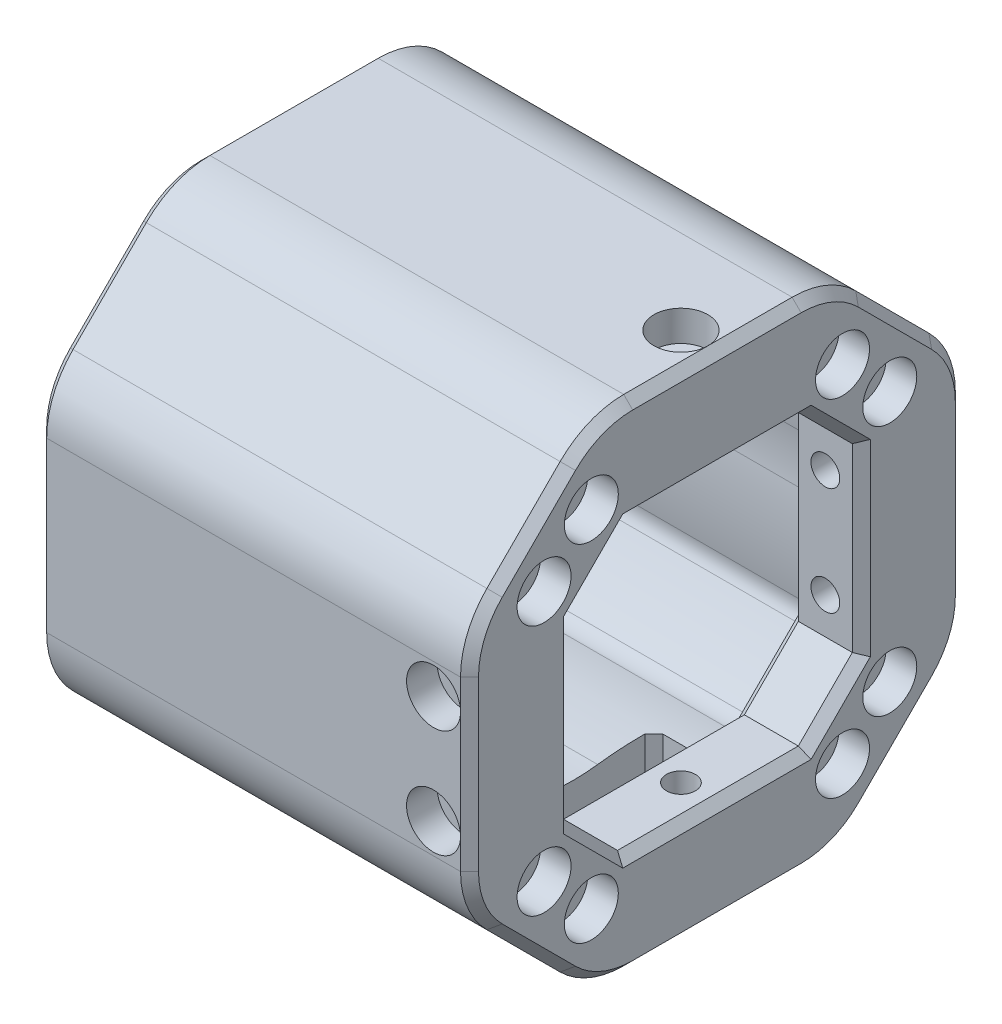
SolidWorks part; units mm, degrees
ref_plane "前视基准面" through (0, 0, 0) normal (0, 0, 1) x (1, 0, 0)
ref_plane "上视基准面" through (0, 0, 0) normal (0, 1, 0) x (1, 0, 0)
ref_plane "右视基准面" through (0, 0, 0) normal (1, 0, 0) x (0, 0, -1)
other "Configuration Table"
sketch "草图1" plane through (0, 0, 0) normal (1, 0, 0) x (0, 0, -1)
  line L1 (-27.5, -27.5) -> (27.5, -27.5)
  line L2 (-27.5, -27.5) -> (-27.5, 27.5)
  line L3 (-27.5, 27.5) -> (27.5, 27.5)
  line L4 (27.5, -27.5) -> (27.5, 27.5)
  line L5 (0, 27.5) -> (0, -27.5) construction
  line L6 (-27.5, 0) -> (27.5, 0) construction
  line L7 (-16.05, 16.05) -> (16.05, 16.05)
  line L8 (-16.05, 16.05) -> (-16.05, -16.05)
  line L9 (-16.05, -16.05) -> (16.05, -16.05)
  line L10 (16.05, 16.05) -> (16.05, -16.05)
  line L11 (0, -16.05) -> (0, 16.05) construction
  line L12 (-16.05, 0) -> (16.05, 0) construction
  circle A0 centre (0, 0) radius 31.25 construction
  circle A8 centre (0, 0) radius 18.05 construction
  dimension "D1" = 62.5
  dimension "D2" = 55
  dimension "D3" = 55
  dimension "D5" = 36.1
  dimension "D4" = 32.1
  dimension "D6" = 32.1
extrude "凸台-拉伸1" add sketch "草图1" along normal blind 8
sketch "草图2" plane through (8, 0, 0) normal (1, 0, 0) x (0, 0, -1)
  line L1 (0, 0) -> (13.9599, 19.2142) construction
  line L2 (0, 0) -> (23.75, 0) construction
  line L3 (0, 0) -> (0, 23.75) construction
  line L4 (0, 0) -> (19.2142, 13.9599) construction
  circle A1 centre (0, 0) radius 23.75 construction
  point P5 (13.9599, 19.2142)
  point P12 (19.2142, -13.9599)
  point P13 (-13.9599, -19.2142)
  point P14 (-19.2142, 13.9599)
  point P16 (19.2142, 13.9599)
  point P48 (13.9599, -19.2142)
  point P49 (-19.2142, -13.9599)
  point P50 (-13.9599, 19.2142)
  dimension "D1" = 47.5
  dimension "D2" = 4
  dimension "D3" = 4
  dimension "D4" = 36
  dimension "D6" = 36
chamfer "倒角1" distance 14 angle 45 4 edges at (4, -27.5, 27.5) (4, -27.5, -27.5) (4, 27.5, -27.5) (4, 27.5, 27.5)
chamfer "倒角2" distance 6 angle 45 4 edges at (4, -16.05, 16.05) (4, -16.05, -16.05) (4, 16.05, -16.05) (4, 16.05, 16.05)
sketch "草图3" plane through (0, 27.5, 0) normal (0, 1, 0) x (1, 0, 0)
  line L3 (8, 13.5) -> (8, -13.5) construction
  line L5 (0, 13.5) -> (0, -13.5) construction
  line L6 (0, 0) -> (4, 0) construction
  point P0 (4, 0)
  dimension "D2" = 4
sketch "草图4" plane through (0, 0, -27.5) normal (0, 0, -1) x (-1, 0, 0)
  line L0 (-4, 13.5) -> (-4, -13.5) construction
  line L1 (0, 13.5) -> (-8, 13.5) construction
  line L2 (-8, -13.5) -> (0, -13.5) construction
  line L3 (-8, 0) -> (0, 0) construction
  line L4 (-8, -13.5) -> (-8, 13.5) construction
  point P0 (-4, 6)
  point P1 (-4, -6)
  dimension "D1" = 6
  dimension "D2" = 6
hole_wizard "M3 六角圆柱头螺钉的柱形沉头孔1" positions "草图2" profile "草图5" counterbore size "M3" standard "GB" end condition through all
sketch "草图5" plane through (8, 19.2142, 13.9599) normal (0, 1, 0) x (0, 0, -1)
  line L0 (0, 0) -> (0, 8)
  line L1 (0, 8) -> (1.6, 8)
  line L3 (1.6, 8) -> (1.6, 3.4)
  line L4 (1.6, 3.4) -> (3, 3.4)
  line L5 (3, 3.4) -> (3, 0)
  line L7 (3, 0) -> (0, 0)
  line L11 (0, -6.35) -> (0, 107.95) construction
  dimension "通孔孔直径" = 3.2
  dimension "通孔孔深度" = 8
  dimension "柱形沉头孔直径" = 6
  dimension "柱形沉头孔深度" = 3.4
hole_wizard "M3 六角圆柱头螺钉的柱形沉头孔2" positions "草图3" profile "草图8" counterbore size "M3" standard "GB" end condition up to next
sketch "草图8" plane through (4, 27.5, 0) normal (1, 0, 0) x (0, 0, 1)
  line L0 (0, 0) -> (0, 11.45)
  line L1 (0, 11.45) -> (1.6, 11.45)
  line L3 (1.6, 11.45) -> (1.6, 3.4)
  line L4 (1.6, 3.4) -> (3, 3.4)
  line L5 (3, 3.4) -> (3, 0)
  line L7 (3, 0) -> (0, 0)
  line L11 (0, -6.35) -> (0, 107.95) construction
  dimension "通孔孔直径" = 3.2
  dimension "通孔孔深度" = 11.45
  dimension "柱形沉头孔直径" = 6
  dimension "柱形沉头孔深度" = 3.4
hole_wizard "M3 六角圆柱头螺钉的柱形沉头孔3" positions "草图4" profile "草图9" counterbore size "M3" standard "GB" end condition up to next
sketch "草图9" plane through (4, 6, -27.5) normal (1, 0, 0) x (0, 1, 0)
  line L0 (0, 0) -> (0, 11.45)
  line L1 (0, 11.45) -> (1.6, 11.45)
  line L3 (1.6, 11.45) -> (1.6, 3.4)
  line L4 (1.6, 3.4) -> (3, 3.4)
  line L5 (3, 3.4) -> (3, 0)
  line L7 (3, 0) -> (0, 0)
  line L11 (0, -6.35) -> (0, 107.95) construction
  dimension "通孔孔直径" = 3.2
  dimension "通孔孔深度" = 11.45
  dimension "柱形沉头孔直径" = 6
  dimension "柱形沉头孔深度" = 3.4
sketch "草图10" plane through (0, 0, 27.5) normal (0, 0, 1) x (1, 0, 0)
  line L0 (4, 13.5) -> (4, -13.5) construction
  line L1 (8, 13.5) -> (0, 13.5) construction
  line L2 (0, -13.5) -> (8, -13.5) construction
  point P6 (4, 6)
  point P7 (4, -6)
  dimension "D1" = 6
  dimension "D2" = 6
hole_wizard "M3 六角圆柱头螺钉的柱形沉头孔4" positions "草图10" profile "草图11" counterbore size "M3" standard "GB" end condition up to next
sketch "草图11" plane through (4, -6, 27.5) normal (1, 0, 0) x (0, -1, 0)
  line L0 (0, 0) -> (0, 11.45)
  line L1 (0, 11.45) -> (1.6, 11.45)
  line L3 (1.6, 11.45) -> (1.6, 3.4)
  line L4 (1.6, 3.4) -> (3, 3.4)
  line L5 (3, 3.4) -> (3, 0)
  line L7 (3, 0) -> (0, 0)
  line L11 (0, -6.35) -> (0, 107.95) construction
  dimension "通孔孔直径" = 3.2
  dimension "通孔孔深度" = 11.45
  dimension "柱形沉头孔直径" = 6
  dimension "柱形沉头孔深度" = 3.4
sketch "草图12" plane through (0, -27.5, 0) normal (0, -1, 0) x (1, 0, 0)
  line L0 (4, 13.5) -> (4, -13.5) construction
  line L1 (8, 13.5) -> (0, 13.5) construction
  line L2 (0, -13.5) -> (8, -13.5) construction
  point P6 (4, 0)
hole_wizard "M3 六角圆柱头螺钉的柱形沉头孔5" positions "草图12" profile "草图13" counterbore size "M3" standard "GB" end condition up to next
sketch "草图13" plane through (4, -27.5, 0) normal (1, 0, 0) x (0, 0, -1)
  line L0 (0, 0) -> (0, 11.45)
  line L1 (0, 11.45) -> (1.6, 11.45)
  line L3 (1.6, 11.45) -> (1.6, 3.4)
  line L4 (1.6, 3.4) -> (3, 3.4)
  line L5 (3, 3.4) -> (3, 0)
  line L7 (3, 0) -> (0, 0)
  line L11 (0, -6.35) -> (0, 107.95) construction
  dimension "通孔孔直径" = 3.2
  dimension "通孔孔深度" = 11.45
  dimension "柱形沉头孔直径" = 6
  dimension "柱形沉头孔深度" = 3.4
fillet "圆角1" radius 10 8 edges at (4, 27.5, 13.5) (4, 13.5, 27.5) (4, 27.5, -13.5) (4, 13.5, -27.5) (4, -13.5, -27.5) (4, -27.5, -13.5) (4, -27.5, 13.5) (4, -13.5, 27.5)
chamfer "倒角4" distance 1 angle 45 24 edges at (8, 0, -16.05) (8, -13.05, -13.05) (8, 13.05, -13.05) (8, 16.05, 0) (8, 13.05, 13.05) (8, -16.05, 0) (8, -13.05, 13.05) (8, 0, 16.05) (8, 0, -27.5) (8, 13.1847, -26.7388) (8, -13.1847, -26.7388) (8, 20.5, -20.5) (8, -20.5, -20.5) (8, 26.7388, -13.1847) (8, -26.7388, -13.1847) (8, 27.5, 0) (8, -27.5, 0) (8, 26.7388, 13.1847) (8, -26.7388, 13.1847) (8, 20.5, 20.5) (8, -20.5, 20.5) (8, 13.1847, 26.7388) (8, -13.1847, 26.7388) (8, 0, 27.5)
ref_plane "基准面2" through (0, 0, 0) normal (-1, 0, 0) x (0, 0, 1)
sketch "草图16" plane through (0, 0, 0) normal (-1, 0, 0) x (0, 0, 1)
  line L8 (0, 0) -> (-21.85, 0) construction
  line L9 (0, 0) -> (0, 21.85) construction
  line L10 (0, 0) -> (0, -21.85) construction
  line L11 (0, 21.75) -> (0, 0) construction
  line L12 (0, 0) -> (21.85, 0) construction
  line L15 (13.9599, 19.2142) -> (0, 0) construction
  line L16 (0, 0) -> (20.5, 20.5) construction
  line L17 (0, -21.75) -> (0, -21.85)
  line L19 (0, 21.75) -> (0, 21.85)
  line L20 (24.5711, 16.4289) -> (16.4289, 24.5711) construction
  line L29 (24.5711, 16.4289) -> (16.4289, 24.5711)
  line L30 (9.3579, 27.5) -> (-9.3579, 27.5)
  line L31 (-16.4289, 24.5711) -> (-24.5711, 16.4289)
  line L32 (-27.5, 9.3579) -> (-27.5, -9.3579)
  line L33 (-24.5711, -16.4289) -> (-16.4289, -24.5711)
  line L34 (-9.3579, -27.5) -> (9.3579, -27.5)
  line L35 (16.4289, -24.5711) -> (24.5711, -16.4289)
  line L36 (27.5, -9.3579) -> (27.5, 9.3579)
  line L37 (24.5711, 16.4289) -> (16.4289, 24.5711)
  line L38 (9.3579, 27.5) -> (-9.3579, 27.5)
  line L39 (-16.4289, 24.5711) -> (-24.5711, 16.4289)
  line L40 (-27.5, 9.3579) -> (-27.5, -9.3579)
  line L41 (-24.5711, -16.4289) -> (-16.4289, -24.5711)
  line L42 (-9.3579, -27.5) -> (9.3579, -27.5)
  line L43 (16.4289, -24.5711) -> (24.5711, -16.4289)
  line L44 (27.5, -9.3579) -> (27.5, 9.3579)
  arc A0 (15.4294, 21.2367) -> (13.5954, 21.6874) centre (13.9599, 19.2142) ccw construction
  arc A1 (2.7345, 21.5774) -> (13.5954, 21.6874) centre (7.7635, 61.26) ccw construction
  arc A2 (2.7345, 21.5774) -> (-2.7345, 21.5774) centre (0, 0) ccw construction
  arc A3 (21.2367, 15.4294) -> (15.4294, 21.2367) centre (0, 0) ccw construction
  arc A4 (21.2367, 15.4294) -> (21.6874, 13.5954) centre (19.2142, 13.9599) cw construction
  arc A5 (21.5774, 2.7345) -> (21.6874, 13.5954) centre (61.26, 7.7635) cw construction
  arc A6 (21.5774, 2.7345) -> (21.5774, -2.7345) centre (0, 0) cw construction
  arc A7 (21.5774, -2.7345) -> (21.6874, -13.5954) centre (61.26, -7.7635) ccw construction
  arc A8 (21.2367, -15.4294) -> (21.6874, -13.5954) centre (19.2142, -13.9599) ccw construction
  arc A9 (21.2367, -15.4294) -> (15.4294, -21.2367) centre (0, 0) cw construction
  arc A10 (15.4294, -21.2367) -> (13.5954, -21.6874) centre (13.9599, -19.2142) cw construction
  arc A11 (2.7345, -21.5774) -> (13.5954, -21.6874) centre (7.7635, -61.26) cw construction
  arc A12 (2.7345, -21.5774) -> (-2.7345, -21.5774) centre (0, 0) cw construction
  arc A13 (-15.4294, -21.2367) -> (-13.5954, -21.6874) centre (-13.9599, -19.2142) ccw construction
  arc A14 (-2.7345, -21.5774) -> (-13.5954, -21.6874) centre (-7.7635, -61.26) ccw construction
  arc A15 (-21.2367, -15.4294) -> (-15.4294, -21.2367) centre (0, 0) ccw construction
  arc A16 (-21.2367, -15.4294) -> (-21.6874, -13.5954) centre (-19.2142, -13.9599) cw construction
  arc A17 (-21.5774, -2.7345) -> (-21.6874, -13.5954) centre (-61.26, -7.7635) cw construction
  arc A18 (-21.5774, 2.7345) -> (-21.5774, -2.7345) centre (0, 0) ccw construction
  arc A19 (-21.5774, 2.7345) -> (-21.6874, 13.5954) centre (-61.26, 7.7635) ccw construction
  arc A20 (-21.2367, 15.4294) -> (-21.6874, 13.5954) centre (-19.2142, 13.9599) ccw construction
  arc A21 (-21.2367, 15.4294) -> (-15.4294, 21.2367) centre (0, 0) cw construction
  arc A22 (-15.4294, 21.2367) -> (-13.5954, 21.6874) centre (-13.9599, 19.2142) cw construction
  arc A23 (-2.7345, 21.5774) -> (-13.5954, 21.6874) centre (-7.7635, 61.26) cw construction
  arc A25 (-2.7345, 21.5774) -> (0, 21.75) centre (0, 0) cw construction
  arc A26 (-2.7345, -21.5774) -> (0, -21.75) centre (0, 0) ccw construction
  arc A28 (2.7471, -21.6766) -> (-2.7471, -21.6766) centre (0, 0) cw
  arc A29 (2.7471, -21.6766) -> (13.5808, -21.7864) centre (7.7635, -61.26) cw
  arc A30 (15.4881, -21.3176) -> (13.5808, -21.7864) centre (13.9599, -19.2142) cw
  arc A31 (21.3176, -15.4881) -> (15.4881, -21.3176) centre (0, 0) cw
  arc A32 (21.3176, -15.4881) -> (21.7864, -13.5808) centre (19.2142, -13.9599) ccw
  arc A33 (21.6766, -2.7471) -> (21.7864, -13.5808) centre (61.26, -7.7635) ccw
  arc A34 (21.6766, 2.7471) -> (21.6766, -2.7471) centre (0, 0) cw
  arc A35 (21.6766, 2.7471) -> (21.7864, 13.5808) centre (61.26, 7.7635) cw
  arc A36 (21.3176, 15.4881) -> (21.7864, 13.5808) centre (19.2142, 13.9599) cw
  arc A37 (21.3176, 15.4881) -> (15.4881, 21.3176) centre (0, 0) ccw
  arc A38 (15.4881, 21.3176) -> (13.5808, 21.7864) centre (13.9599, 19.2142) ccw
  arc A39 (2.7471, 21.6766) -> (13.5808, 21.7864) centre (7.7635, 61.26) ccw
  arc A40 (2.7471, 21.6766) -> (-2.7471, 21.6766) centre (0, 0) ccw
  arc A41 (-2.7471, 21.6766) -> (-13.5808, 21.7864) centre (-7.7635, 61.26) cw
  arc A42 (-15.4881, 21.3176) -> (-13.5808, 21.7864) centre (-13.9599, 19.2142) cw
  arc A43 (-21.3176, 15.4881) -> (-15.4881, 21.3176) centre (0, 0) cw
  arc A44 (-21.3176, 15.4881) -> (-21.7864, 13.5808) centre (-19.2142, 13.9599) ccw
  arc A45 (-21.6766, 2.7471) -> (-21.7864, 13.5808) centre (-61.26, 7.7635) ccw
  arc A46 (-21.6766, 2.7471) -> (-21.6766, -2.7471) centre (0, 0) ccw
  arc A47 (-21.6766, -2.7471) -> (-21.7864, -13.5808) centre (-61.26, -7.7635) cw
  arc A48 (-21.3176, -15.4881) -> (-21.7864, -13.5808) centre (-19.2142, -13.9599) cw
  arc A49 (-21.3176, -15.4881) -> (-15.4881, -21.3176) centre (0, 0) ccw
  arc A50 (-15.4881, -21.3176) -> (-13.5808, -21.7864) centre (-13.9599, -19.2142) ccw
  arc A51 (-2.7471, -21.6766) -> (-13.5808, -21.7864) centre (-7.7635, -61.26) ccw
  arc A52 (-2.7471, -21.6766) -> (0, -21.85) centre (0, 0) ccw
  arc A61 (16.4289, 24.5711) -> (9.3579, 27.5) centre (9.3579, 17.5) ccw
  arc A62 (-9.3579, 27.5) -> (-16.4289, 24.5711) centre (-9.3579, 17.5) ccw
  arc A63 (-24.5711, 16.4289) -> (-27.5, 9.3579) centre (-17.5, 9.3579) ccw
  arc A64 (-27.5, -9.3579) -> (-24.5711, -16.4289) centre (-17.5, -9.3579) ccw
  arc A65 (-16.4289, -24.5711) -> (-9.3579, -27.5) centre (-9.3579, -17.5) ccw
  arc A66 (9.3579, -27.5) -> (16.4289, -24.5711) centre (9.3579, -17.5) ccw
  arc A67 (24.5711, -16.4289) -> (27.5, -9.3579) centre (17.5, -9.3579) ccw
  arc A68 (27.5, 9.3579) -> (24.5711, 16.4289) centre (17.5, 9.3579) ccw
  arc A69 (16.4289, 24.5711) -> (9.3579, 27.5) centre (9.3579, 17.5) ccw
  arc A70 (-9.3579, 27.5) -> (-16.4289, 24.5711) centre (-9.3579, 17.5) ccw
  arc A71 (-24.5711, 16.4289) -> (-27.5, 9.3579) centre (-17.5, 9.3579) ccw
  arc A72 (-27.5, -9.3579) -> (-24.5711, -16.4289) centre (-17.5, -9.3579) ccw
  arc A73 (-16.4289, -24.5711) -> (-9.3579, -27.5) centre (-9.3579, -17.5) ccw
  arc A74 (9.3579, -27.5) -> (16.4289, -24.5711) centre (9.3579, -17.5) ccw
  arc A75 (24.5711, -16.4289) -> (27.5, -9.3579) centre (17.5, -9.3579) ccw
  arc A76 (27.5, 9.3579) -> (24.5711, 16.4289) centre (17.5, 9.3579) ccw
  dimension "D1" = 0
extrude "凸台-拉伸2" add sketch "草图16" along normal blind 40 contours L44 A76 L37 A69 L38 A70 L39 A71 L40 A72 L41 A73 L42 A74 L43 A75 A28 A51 A50 A49 A48 A47 A46 A45 A44 A43 A42 A41 A40 A39 A38 A37 A36 A35 A34 A33 A32 A31 A30 A29
chamfer "倒角5" distance 1 angle 45 48 edges at (-40, -13.1847, 26.7388) (-40, -20.5, 20.5) (-40, -26.7388, 13.1847) (-40, -27.5, 0) (-40, -26.7388, -13.1847) (-40, -20.5, -20.5) (-40, -13.1847, -26.7388) (-40, 0, -27.5) (-40, 13.1847, -26.7388) (-40, 20.5, -20.5) (-40, 26.7388, -13.1847) (-40, 27.5, 0) (-40, 26.7388, 13.1847) (-40, 20.5, 20.5) (-40, 13.1847, 26.7388) (-40, 0, 27.5) (-40, -21.3621, 8.1677) (-40, -21.739, 14.5805) (-40, -18.6323, 18.6323) (-40, -14.5805, 21.739) (-40, -8.1677, 21.3621) (-40, 0, 21.85) (-40, 8.1677, 21.3621) (-40, 14.5805, 21.739) (-40, 18.6323, 18.6323) (-40, 21.739, 14.5805) (-40, 21.3621, 8.1677) (-40, 21.85, 0) (-40, 21.3621, -8.1677) (-40, 21.739, -14.5805) (-40, 18.6323, -18.6323) (-40, 14.5805, -21.739) (-40, 8.1677, -21.3621) (-40, 0, -21.85) (-40, -8.1677, -21.3621) (-40, -14.5805, -21.739) (-40, -18.6323, -18.6323) (-40, -21.739, -14.5805) (-40, -21.3621, -8.1677) (-40, -21.85, 0) (0, 13.05, 13.05) (0, 16.05, 0) (0, 13.05, -13.05) (0, 0, -16.05) (0, -13.05, -13.05) (0, -16.05, 0) (0, -13.05, 13.05) (0, 0, 16.05)
sketch "草图18" plane through (0, -27.5, 0) normal (0, -1, 0) x (1, 0, 0)
  line L0 (-39, 0) -> (-8, 0)
  line L1 (-39, 9.3579) -> (-39, -9.3579) construction
  line L2 (8, 9.3579) -> (8, -9.3579) construction
  line L3 (-8, 9) -> (0, 9)
  line L4 (-8, 9) -> (-8, -9)
  line L5 (-8, -9) -> (0, -9)
  line L6 (0, 9) -> (0, -9)
  point P9 (-8, 0)
  dimension "D1" = 8
  dimension "D2" = 18
  dimension "D3" = 8
extrude "切除-拉伸1" cut sketch "草图18" against normal blind 40 contours L6 L3 L4 L5
chamfer "倒角6" distance 1 angle 45 4 edges at (-8, -24.4396, -9) (0, -24.4396, -9) (-8, -24.4396, 9) (0, -24.4396, 9)
chamfer "倒角7" distance 1 angle 45 8 edges at (-7.5, -27.5, 8.5) (-8, -27.5, 0) (-7.5, -27.5, -8.5) (-4, -27.5, -9) (-0.5, -27.5, -8.5) (0, -27.5, 0) (-0.5, -27.5, 8.5) (-4, -27.5, 9)
